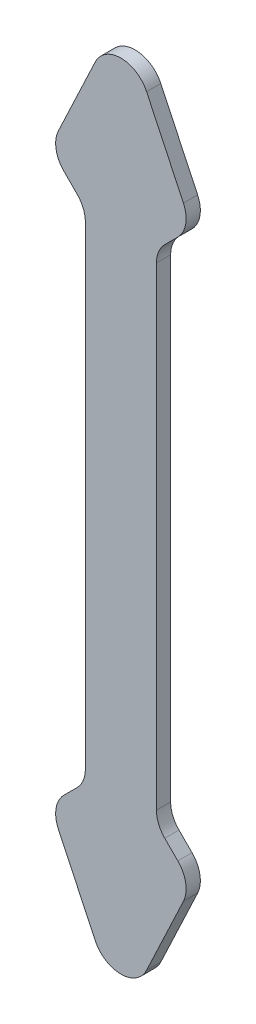
SolidWorks part; units mm, degrees
ref_plane "Front Plane" through (0, 0, 0) normal (0, 0, 1) x (1, 0, 0)
ref_plane "Top Plane" through (0, 0, 0) normal (0, 1, 0) x (1, 0, 0)
ref_plane "Right Plane" through (0, 0, 0) normal (1, 0, 0) x (0, 0, -1)
sketch "Sketch1" plane through (0, 0, 0) normal (0, 0, 1) x (1, 0, 0)
  line L0 (-3.6178, 53.5314) -> (-8.7996, 42.545)
  line L1 (-8.0103, 38.0103) -> (-6.1716, 36.1716)
  line L2 (-5, 33.3431) -> (-5, -33.3431)
  line L3 (-5, 0) -> (0, 0) construction
  line L4 (0, 0) -> (0, 61.2017) construction
  line L5 (5, 33.3431) -> (5, -33.3431)
  line L6 (8.0103, 38.0103) -> (6.1716, 36.1716)
  line L7 (3.6178, 53.5314) -> (8.7996, 42.545)
  line L8 (-8.0103, -38.0103) -> (-6.1716, -36.1716)
  line L9 (8.0103, -38.0103) -> (6.1716, -36.1716)
  line L10 (3.6178, -53.5314) -> (8.7996, -42.545)
  line L11 (-3.6178, -53.5314) -> (-8.7996, -42.545)
  arc A0 (5, 33.3431) -> (6.1716, 36.1716) centre (9, 33.3431) cw
  arc A1 (-6.1716, 36.1716) -> (-5, 33.3431) centre (-9, 33.3431) cw
  arc A2 (6.1716, -36.1716) -> (5, -33.3431) centre (9, -33.3431) cw
  arc A3 (-6.1716, -36.1716) -> (-5, -33.3431) centre (-9, -33.3431) ccw
  arc A4 (8.0103, 38.0103) -> (8.7996, 42.545) centre (5.1818, 40.8387) ccw
  arc A5 (-8.7996, 42.545) -> (-8.0103, 38.0103) centre (-5.1818, 40.8387) ccw
  arc A6 (8.0103, -38.0103) -> (8.7996, -42.545) centre (5.1818, -40.8387) cw
  arc A7 (-8.0103, -38.0103) -> (-8.7996, -42.545) centre (-5.1818, -40.8387) ccw
  arc A8 (3.6178, -53.5314) -> (-3.6178, -53.5314) centre (0, -51.825) cw
  arc A9 (-3.6178, 53.5314) -> (3.6178, 53.5314) centre (0, 51.825) cw
  point P2 (-4.0734, 69.0527)
  point P11 (5, 0)
  point P17 (5, 35)
  point P20 (-5, 35)
  point P23 (5, -35)
  point P26 (-5, -35)
  point P29 (10, 40)
  point P32 (-10, 40)
  point P35 (10, -40)
  point P38 (-10, -40)
  point P41 (0, -61.2017)
  point P45 (0, 55.825)
  point P46 (0, -55.825)
  dimension "D6" = 4
  dimension "D1" = 40
  dimension "D2" = 111.65
  dimension "D3" = 10
  dimension "D4" = 5
  dimension "D5" = 35
extrude "Boss-Extrude1" add sketch "Sketch1" along normal blind 2
